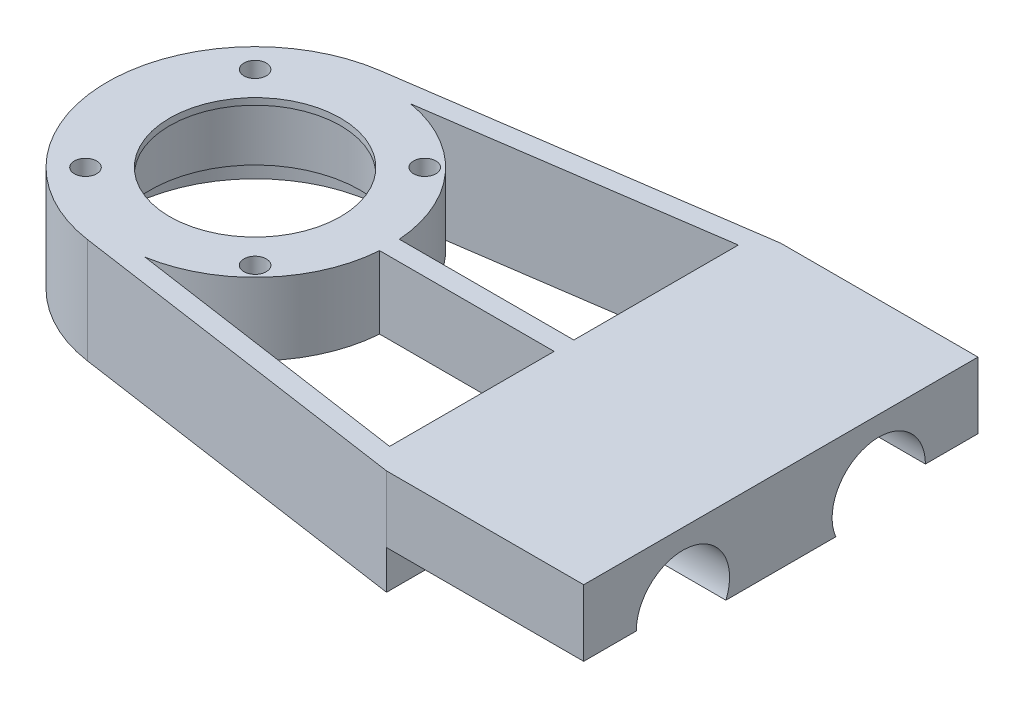
SolidWorks part; units mm, degrees
material "3.1355 (EN-AW 2024)"
ref_plane "Front" through (0, 0, 0) normal (0, 0, 1) x (1, 0, 0)
ref_plane "Top" through (0, 0, 0) normal (0, 1, 0) x (1, 0, 0)
ref_plane "Right" through (0, 0, 0) normal (1, 0, 0) x (0, 0, -1)
sketch "Эскиз1" plane through (0, 0, 0) normal (0, 1, 0) x (1, 0, 0)
  line L0 (0, 0) -> (0, 60)
  line L1 (0, 60) -> (-30, 60)
  line L2 (0, 30) -> (-130, 30) construction
  line L3 (-30, 60) -> (-30, 30) construction
  line L4 (-30, 60) -> (-83.2348, 52.2663)
  line L5 (-30, 0) -> (-83.2348, 7.7337)
  line L6 (0, 0) -> (-30, 0)
  circle A0 centre (-80, 30) radius 22.5 construction
  arc A1 (-83.2348, 52.2663) -> (-83.2348, 7.7337) centre (-80, 30) ccw
  dimension "D2" = 45
  dimension "D1" = 60
  dimension "D3" = 30
  dimension "D4" = 130
  dimension "D5" = 50
extrude "Бобышка-Вытянуть1" add sketch "Эскиз1" along normal blind 16
sketch "Эскиз2" plane through (0, 0, 0) normal (0, -1, 0) x (1, 0, 0)
  circle A0 centre (-80, -30) radius 16
  dimension "D1" = 32
extrude "Вырез-Вытянуть1" cut sketch "Эскиз2" against normal offset from surface (15 mm away) 1 up to face at (-40.9558, 16, -30)
sketch "Эскиз3" plane through (0, 15, 0) normal (0, -1, 0) x (1, 0, 0)
  circle A0 centre (-80, -30) radius 13
  dimension "D1" = 26
extrude "Вырез-Вытянуть2" cut sketch "Эскиз3" against normal through all
sketch "Эскиз4" plane through (0, 0, 0) normal (0, -1, 0) x (1, 0, 0)
  circle A0 centre (-80, -30) radius 20.5
  dimension "D1" = 41
extrude "Вырез-Вытянуть3" cut sketch "Эскиз4" against normal offset from surface (5 mm away) 10 up to face at (-80, 15, -43)
sketch "Эскиз5" plane through (0, 5, 0) normal (0, -1, 0) x (1, 0, 0)
  line L0 (-80, -30) -> (-98.25, -30) construction
  line L1 (-80, -30) -> (-92.9047, -17.0953) construction
  line L2 (-80, -30) -> (-67.0953, -17.0953) construction
  line L3 (-80, -30) -> (-67.0953, -42.9047) construction
  line L4 (-80, -30) -> (-92.9047, -42.9047) construction
  circle A0 centre (-80, -30) radius 18.25 construction
  circle A1 centre (-80, -30) radius 20.5 construction
  point P13 (-80, -30)
  dimension "D1" = 36.5
  dimension "D2" = 45
  dimension "D3" = 4
hole_wizard "Отверстие с зазором M31" [suppressed] positions "Эскиз7" profile "Эскиз6" hole size "M3" standard "Ansi Metric"
sketch "Эскиз7" plane through (0, 5, 0) normal (0, -1, 0) x (-1, 0, 0)
  line L0 (0, 30) -> (130, 30) construction
  circle A0 centre (80, 30) radius 18.25 construction
  point P0 (80, 11.75)
  point P4 (98.25, 30)
  point P8 (80, 48.25)
  point P10 (61.75, 30)
sketch "Эскиз6" plane through (-80, 5, -11.75) normal (1, 0, 0) x (0, 0, -1)
  line L0 (0, 0) -> (0, 11)
  line L1 (0, 11) -> (1.7, 11)
  line L2 (1.7, 11) -> (1.7, 0)
  line L5 (1.7, 0) -> (0, 0)
  line L11 (0, -6.35) -> (0, 107.95) construction
  dimension "Диаметр сквозного отверстия" = 3.4
  dimension "Глубина сквозного отверстия" = 11
hole_wizard "Отверстие с зазором M32" positions "Эскиз19" profile "Эскиз18" hole size "M3" standard "Ansi Metric" end condition through all
sketch "Эскиз19" plane through (0, 5, 0) normal (0, -1, 0) x (-1, 0, 0)
  point P0 (92.9047, 17.0953)
  point P3 (67.0953, 17.0953)
  point P6 (67.0953, 42.9047)
  point P9 (92.9047, 42.9047)
sketch "Эскиз18" plane through (-92.9047, 5, -17.0953) normal (1, 0, 0) x (0, 0, -1)
  line L0 (0, 0) -> (0, 11)
  line L1 (0, 11) -> (1.7, 11)
  line L2 (1.7, 11) -> (1.7, 0)
  line L5 (1.7, 0) -> (0, 0)
  line L11 (0, -6.35) -> (0, 107.95) construction
  dimension "Диаметр сквозного отверстия" = 3.4
  dimension "Глубина сквозного отверстия" = 11
sketch "Эскиз8" plane through (0, 0, 0) normal (1, 0, 0) x (0, 0, -1)
  line L0 (30, 16) -> (30, 0) construction
  line L1 (8, 5.9) -> (0, 5.9)
  line L2 (0, 16) -> (60, 16) construction
  line L3 (52, 5.9) -> (60, 5.9)
  line L4 (21.6401, 3.1366) -> (38.3599, 3.1366)
  line L5 (52.5, 0) -> (7.5, 0) construction
  line L6 (0, 16) -> (0, 0) construction
  line L7 (48.8497, 0) -> (60, 0)
  line L8 (19.0497, 0) -> (40.9503, 0)
  line L18 (0, 0) -> (60, 0)
  line L19 (60, 0) -> (60, 16)
  line L20 (60, 16) -> (0, 16)
  line L21 (0, 16) -> (0, 0)
  line L22 (0, 0) -> (11.1503, 0)
  line L23 (60, 0) -> (60, 5.9)
  line L25 (0, 5.9) -> (0, 0)
  circle A0 centre (15.1, 5.9) radius 7.1
  circle A1 centre (44.9, 5.9) radius 7.1
  line M3 (0, 0) -> (60, 0)
  line M4 (60, 0) -> (60, 16)
  line M6 (0, 16) -> (0, 0)
  dimension "D1" = 14.2
  dimension "D3" = 10.1
  dimension "D4" = 0
  dimension "D2" = 15.1
extrude "Вырез-Вытянуть8" cut sketch "Эскиз8" against normal blind 30 contours A0 M3 | A0 L1 M6 M3 | L4 L0 L8 A1 | A1 M3 | L3 A1 M3 M4 | L0 L4 A0 M3
sketch "Эскиз12" plane through (0, 0, 0) normal (0, -1, 0) x (1, 0, 0)
  line L0 (-30, 0) -> (-83.2348, -7.7337) construction
  line L1 (-30, -60) -> (-83.2348, -52.2663) construction
  line L2 (-30, -60) -> (-30, -30) construction
  line L3 (-30, 0) -> (-76.5229, -6.7587)
  line L4 (-30, -60) -> (-76.5229, -53.2413)
  line L5 (-30, -60) -> (-30, 0)
  circle A2 centre (-80, -30) radius 23.5
  arc A3 (-76.5229, -53.2413) -> (-76.5229, -6.7587) centre (-80, -30) ccw
  dimension "D1" = 3
extrude "Вырез-Вытянуть9" [suppressed] cut sketch "Эскиз12" against normal up to surface (5.9 mm away)
sketch "Эскиз13" [suppressed] plane through (0, 3.1366, 0) normal (0, -1, 0) x (1, 0, 0)
  line L4 (-27, -24.6401) -> (-27, -35.3599)
  line L5 (-27, -24.6401) -> (-27, -35.3599)
  line L26 (-3, -35.3599) -> (-3, -24.6401)
  line L27 (-3, -24.6401) -> (-27, -24.6401)
  line L36 (-27, -35.3599) -> (-3, -35.3599)
  arc A0 (-76.5229, -53.2413) -> (-76.5229, -6.7587) centre (-80, -30) ccw construction
  arc A1 (-69.8248, -51.1829) -> (-69.8248, -8.8171) centre (-80, -30) ccw
  dimension "D1" = 3
extrude "Вырез-Вытянуть10" [suppressed] cut sketch "Эскиз13" against normal through all
sketch "Эскиз14" plane through (0, 0, 0) normal (0, -1, 0) x (1, 0, 0)
  line L9 (-33, -56.5327) -> (-82.8035, -49.2974)
  line L10 (-33, -3.4673) -> (-33, -56.5327)
  line L11 (-82.8035, -10.7026) -> (-33, -3.4673)
  line L12 (-33, -56.5327) -> (-76.5446, -50.2067)
  line L13 (-33, -3.4673) -> (-33, -56.5327)
  line L14 (-76.5446, -9.7933) -> (-33, -3.4673)
  circle A0 centre (-80, -30) radius 20.5 construction
  arc A1 (-76.5446, -50.2067) -> (-76.5446, -9.7933) centre (-80, -30) ccw
  dimension "D1" = 3
extrude "Вырез-Вытянуть11" cut sketch "Эскиз14" against normal through all
sketch "Эскиз15" plane through (0, 5, 0) normal (0, -1, 0) x (1, 0, 0)
  line L0 (-59.5, -30) -> (-33, -30) construction
  line L1 (-33, -56.5327) -> (-33, -3.4673) construction
  line L2 (-59.555, -31.5) -> (-33, -31.5)
  line L3 (-59.555, -28.5) -> (-33, -28.5)
  line L4 (-59.5, -28.5) -> (-33, -28.5) construction
  line L5 (-59.5, -31.5) -> (-33, -31.5) construction
  line L6 (-33, -28.5) -> (-33, -31.5)
  arc A0 (-76.5446, -50.2067) -> (-76.5446, -9.7933) centre (-80, -30) ccw construction
  arc A1 (-59.555, -31.5) -> (-59.555, -28.5) centre (-80, -30) ccw
  dimension "D1" = 1.5
  dimension "D2" = 1.5
extrude "Бобышка-Вытянуть2" add sketch "Эскиз15" against normal through all
equation "\"D4@Эскиз1\"=\"D3@Эскиз1\"+100"
equation "\"D1@Эскиз5\"=32+4.5"
equation "\"D2@Эскиз8\"=8+\"D1@Эскиз8\"/2"
equation "\"D3@Эскиз8\"=3+\"D1@Эскиз8\"/2"
